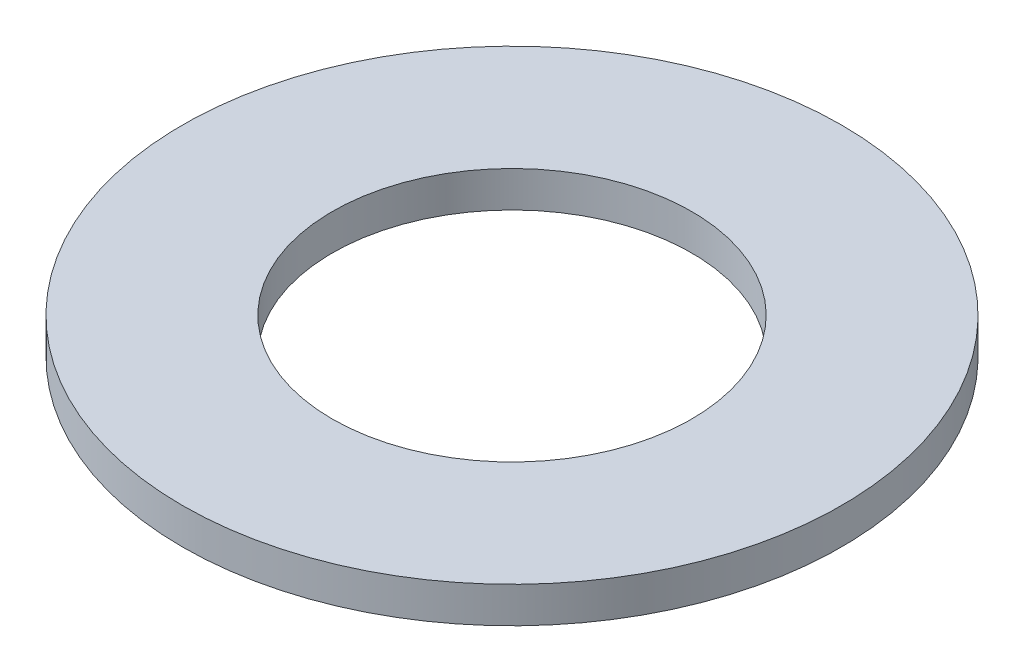
SolidWorks part; units mm, degrees
ref_plane "Front Plane" through (0, 0, 0) normal (0, 0, 1) x (1, 0, 0)
ref_plane "Top Plane" through (0, 0, 0) normal (0, 1, 0) x (1, 0, 0)
ref_plane "Right Plane" through (0, 0, 0) normal (1, 0, 0) x (0, 0, -1)
sketch "Sketch1" plane through (0, 0, 0) normal (0, 1, 0) x (1, 0, 0)
  circle A0 centre (0, 0) radius 55
  dimension "FLANGE_OD" = 110
extrude "Boss-Extrude1" add sketch "Sketch1" along normal blind 6
sketch "Sketch2" plane through (0, 0, 0) normal (0, 1, 0) x (1, 0, 0)
  circle A0 centre (0, 0) radius 30
  dimension "BORE_D" = 60
extrude "Cut-Extrude1" cut sketch "Sketch2" along normal through all
sketch "Sketch3" plane through (0, 6, 0) normal (0, 1, 0) x (1, 0, 0)
  circle A0 centre (0, 0) radius 20.5746 construction
  circle A1 centre (-20.5746, 0) radius 2.4908
  dimension "BOLT_D" = 4.9817
  dimension "BOLT_PCD" = 41.1492
extrude "Cut-Extrude2" cut sketch "Sketch3" against normal blind 4.3463 rebuild error yes
pattern_circular "CirPattern1" count 5 over 360 rebuild error yes
